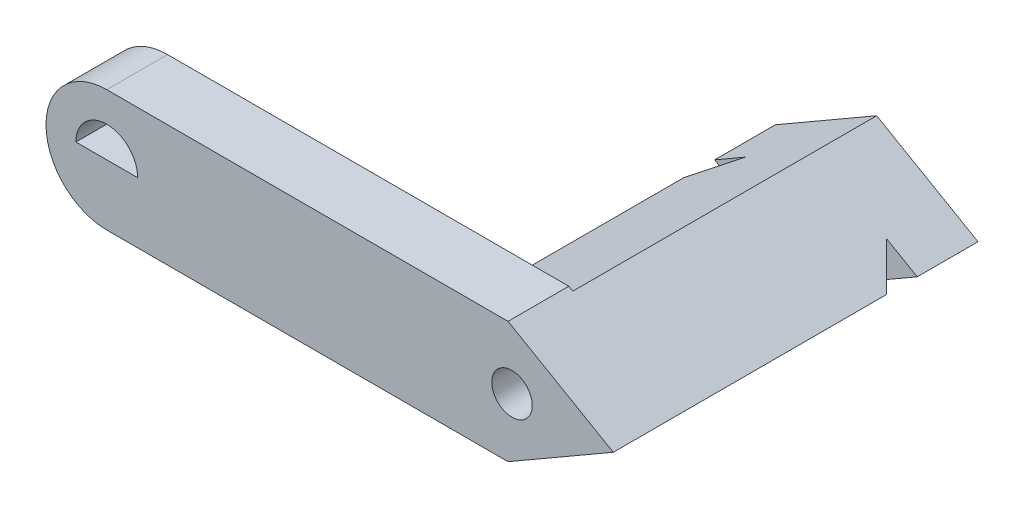
SolidWorks part; units mm, degrees
ref_plane "Front" through (0, 0, 0) normal (0, 0, 1) x (1, 0, 0)
ref_plane "Top" through (0, 0, 0) normal (0, 1, 0) x (1, 0, 0)
ref_plane "Right" through (0, 0, 0) normal (1, 0, 0) x (0, 0, -1)
sketch "Sketch1" plane through (0, 0, 0) normal (0, 0, 1) x (1, 0, 0)
  line L0 (-25, 0) -> (0, 0)
  line L1 (-25, -12) -> (25, -12)
  line L2 (0, 0) -> (25, 0)
  line L3 (25, 0) -> (25, -12)
  arc A0 (-25, 0) -> (-25, -12) centre (-25, -6) ccw
  arc A1 (25, -12) -> (25, 0) centre (25, -6) ccw construction
  dimension "D2" = 6
  dimension "D1" = 50
extrude "Boss-Extrude1" add sketch "Sketch1" along normal blind 6
sketch "Sketch2" plane through (0, 0, 6) normal (0, 0, 1) x (1, 0, 0)
  line L0 (-28.05, -6) -> (-21.95, -6)
  arc A0 (-21.95, -6) -> (-28.05, -6) centre (-25, -6) ccw
  dimension "D1" = 6.1
extrude "Cut-Extrude1" cut sketch "Sketch2" against normal up to next
sketch "Sketch3" plane through (0, 0, 0) normal (0, 0, -1) x (-1, 0, 0)
  line L0 (-25, 0) -> (-5, 0)
  line L1 (-25, 0) -> (25, 0) construction
  line L2 (-5, 0) -> (-5, -6)
  line L3 (-5, -6) -> (-5, -12)
  line L4 (25, -12) -> (-25, -12) construction
  line L5 (-5, -12) -> (-25, -12)
  line L6 (-25, 0) -> (-25, -12)
  dimension "D1" = 20
extrude "Boss-Extrude2" add sketch "Sketch3" along normal blind 30
sketch "Sketch4" plane through (5, 0, 0) normal (-1, 0, 0) x (0, 0, 1)
  line L0 (-20.9689, -6) -> (-24, -4.25)
  line L1 (-24, -4.25) -> (-24, -7.75)
  line L2 (-24, -7.75) -> (-20.9689, -6)
  line L3 (-30, -12) -> (-30, 0) construction
  point P4 (-24, -6)
  point P9 (-30, -6)
  dimension "D1" = 60
  dimension "D3" = 6
  dimension "D2" = 3.5
extrude "Cut-Extrude2" cut sketch "Sketch4" against normal up to next
sketch "Sketch5" plane through (0, 0, 6) normal (0, 0, 1) x (1, 0, 0)
  line L0 (5, -6) -> (25, -6) construction
  line L1 (5, -12) -> (5, 0) construction
  line L2 (25, 0) -> (25, -12) construction
  circle A0 centre (15, -6) radius 2
  point P10 (15, -6)
  dimension "D1" = 4
extrude "Cut-Extrude3" cut sketch "Sketch5" against normal through all
sketch "Sketch6" plane through (0, 0, -30) normal (0, 0, 1) x (1, 0, 0)
  line L0 (11.4, -3.9215) -> (11.4, -8.0785)
  line L1 (11.4, -8.0785) -> (15, -10.1569)
  line L2 (15, -10.1569) -> (18.6, -8.0785)
  line L3 (18.6, -8.0785) -> (18.6, -3.9215)
  line L4 (18.6, -3.9215) -> (15, -1.8431)
  line L5 (15, -1.8431) -> (11.4, -3.9215)
  line L6 (15, -1.8431) -> (15, -10.1569) construction
  line L7 (11.4, -3.9215) -> (18.6, -8.0785) construction
  line L8 (11.4, -8.0785) -> (18.6, -3.9215) construction
  circle A0 centre (15, -6) radius 2 construction
  point P10 (15, -6)
  dimension "D1" = 7.2
  dimension "D2" = 7.2
  dimension "D3" = 7.2
chamfer "Chamfer1" distance 6 angle 60 2 edges at (5, 0, -15) (5, -12, -15) first distance on face at (5, -6, -22.9896)
chamfer "Chamfer2" distance 6 angle 60 2 edges at (25, -12, -12) (25, 0, -12) first distance on face at (25, -6, -22.9896)
extrude "Cut-Extrude4" cut sketch "Sketch6" along normal blind 4
